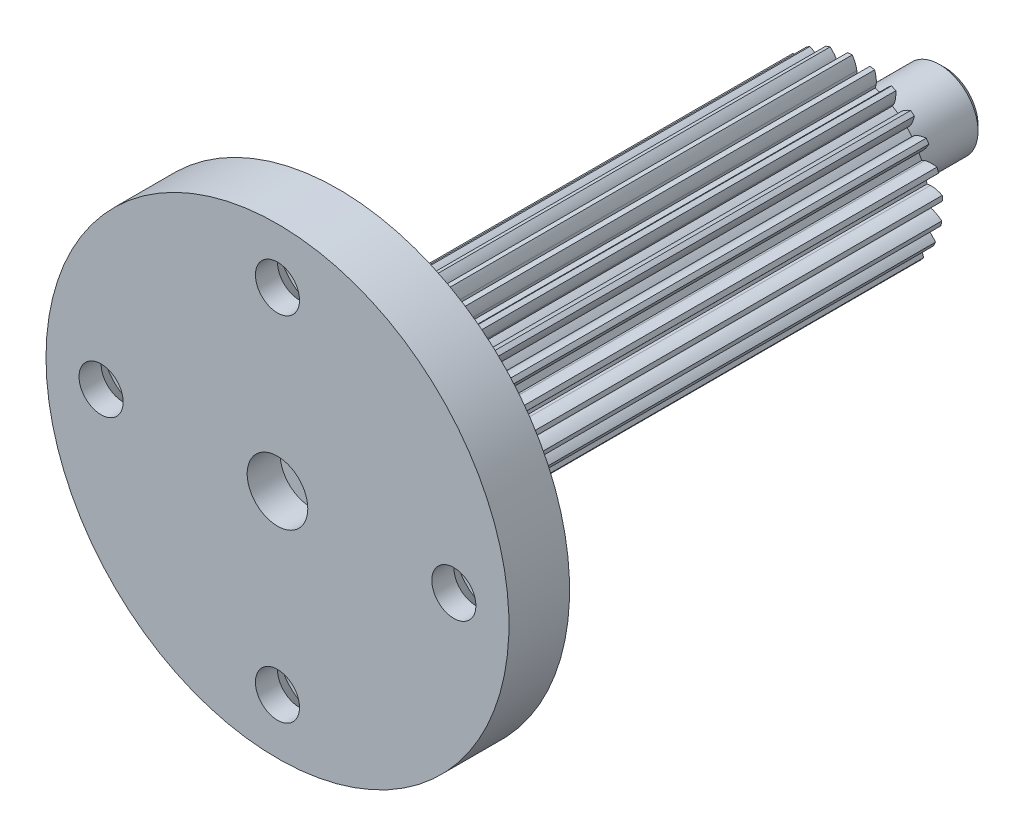
SolidWorks part; units mm, degrees
material "ABS"
ref_plane "Front Plane" through (0, 0, 0) normal (0, 0, 1) x (1, 0, 0)
ref_plane "Top Plane" through (0, 0, 0) normal (0, 1, 0) x (1, 0, 0)
ref_plane "Right Plane" through (0, 0, 0) normal (1, 0, 0) x (0, 0, -1)
sketch "Sketch1" plane through (0, 0, 0) normal (0, 0, 1) x (1, 0, 0)
  circle A0 centre (0, 0) radius 7.8
  dimension "D1" = 15.6
extrude "Boss-Extrude1" add sketch "Sketch1" along normal mid plane 48.5566
sketch "Sketch2" plane through (0, 0, 0) normal (0, 0, 1) x (1, 0, 0)
  line L0 (0, 0) -> (6.7658, 0) construction
  line L1 (0, 0) -> (7.1908, -0.3638) construction
  line L2 (0, 0) -> (6.7312, -0.6828) construction
  line L3 (6.7658, 0) -> (6.45, 0)
  line L4 (6.7312, -0.6828) -> (6.4171, -0.6509)
  circle A0 centre (0, 0) radius 7.2 construction
  circle A1 centre (0, 0) radius 6.7658 construction
  circle A2 centre (0, 0) radius 6.45
  circle A3 centre (0, 0) radius 7.8 construction
  circle A4 centre (0, 0) radius 7.8
  spline S0 degree 4 poles (6.7658, 0) (6.7681, 0) (6.7746, 0.0002) (6.7946, 0.0015) (6.834, 0.0059) (6.8824, 0.014) (6.9379, 0.0258) (6.9911, 0.0392) (7.0364, 0.052) (7.0815, 0.0658) (7.1262, 0.0806) (7.18, 0.0998) (7.2443, 0.1244) (7.3189, 0.1557) (7.4027, 0.194) (7.4874, 0.2362) (7.57, 0.2801) (7.6527, 0.3273) (7.732, 0.375) (7.8135, 0.4274) (7.8882, 0.4772) (7.9707, 0.5362) (8.037, 0.5847) (8.1231, 0.652) (8.1736, 0.6927) (8.2323, 0.7415) (8.2581, 0.7637) (8.274, 0.7774) knots 0 0 0 0 0 0.005377 0.015084 0.04661 0.092111 0.119476 0.146842 0.174209 0.201575 0.228941 0.256307 0.307035 0.361767 0.4165 0.471232 0.525964 0.580697 0.635429 0.690161 0.744894 0.799626 0.854358 0.909091 0.954545 1 1 1 1 1 construction
  spline S1 degree 4 poles (6.7658, 0) (6.7681, 0) (6.7746, 0.0002) (6.7946, 0.0015) (6.834, 0.0059) (6.8824, 0.014) (6.9379, 0.0258) (6.9911, 0.0392) (7.0364, 0.052) (7.0815, 0.0658) (7.1262, 0.0806) (7.18, 0.0998) (7.2443, 0.1244) (7.3189, 0.1557) (7.4027, 0.194) (7.4874, 0.2362) (7.57, 0.2801) (7.6527, 0.3273) (7.732, 0.375) (7.8135, 0.4274) (7.8882, 0.4772) (7.9707, 0.5362) (8.037, 0.5847) (8.1045, 0.6374) (8.1372, 0.6634) (8.1538, 0.6769) knots 0 0 0 0 0 0.005377 0.015084 0.04661 0.092111 0.119476 0.146842 0.174209 0.201575 0.228941 0.256307 0.307035 0.361767 0.4165 0.471232 0.525964 0.580697 0.635429 0.690161 0.744894 0.799626 0.854358 0.909091 0.909091 0.909091 0.909091 0.909091
  spline S2 degree 4 poles (6.7312, -0.6828) (6.7335, -0.6831) (6.74, -0.6839) (6.7598, -0.6872) (6.7985, -0.6955) (6.8459, -0.7085) (6.8999, -0.7258) (6.9515, -0.7446) (6.9953, -0.7618) (7.0387, -0.7801) (7.0816, -0.7994) (7.1333, -0.8239) (7.1948, -0.8549) (7.2658, -0.8935) (7.3454, -0.9401) (7.4254, -0.9906) (7.5031, -1.0426) (7.5806, -1.0979) (7.6547, -1.1534) (7.7304, -1.2137) (7.7997, -1.2709) (7.8759, -1.3379) (7.937, -1.3928) (8.0159, -1.4684) (8.062, -1.514) (8.1154, -1.5685) (8.1388, -1.5932) (8.1533, -1.6084) knots 0 0 0 0 0 0.005377 0.015084 0.04661 0.092111 0.119476 0.146842 0.174209 0.201575 0.228941 0.256307 0.307035 0.361767 0.4165 0.471232 0.525964 0.580697 0.635429 0.690161 0.744894 0.799626 0.854358 0.909091 0.954545 1 1 1 1 1 construction
  spline S3 degree 4 poles (6.7312, -0.6828) (6.7335, -0.6831) (6.74, -0.6839) (6.7598, -0.6872) (6.7985, -0.6955) (6.8459, -0.7085) (6.8999, -0.7258) (6.9515, -0.7446) (6.9953, -0.7618) (7.0387, -0.7801) (7.0816, -0.7994) (7.1333, -0.8239) (7.1948, -0.8549) (7.2658, -0.8935) (7.3454, -0.9401) (7.4254, -0.9906) (7.5031, -1.0426) (7.5806, -1.0979) (7.6547, -1.1534) (7.7304, -1.2137) (7.7997, -1.2709) (7.8759, -1.3379) (7.937, -1.3928) (7.9988, -1.452) (8.0287, -1.4812) (8.0439, -1.4963) knots 0 0 0 0 0 0.005377 0.015084 0.04661 0.092111 0.119476 0.146842 0.174209 0.201575 0.228941 0.256307 0.307035 0.361767 0.4165 0.471232 0.525964 0.580697 0.635429 0.690161 0.744894 0.799626 0.854358 0.909091 0.909091 0.909091 0.909091 0.909091
  dimension "D1" = 14.4
  dimension "D2" = 13.5316
  dimension "D3" = 12.9
  dimension "D4" = 2.896
  dimension "D5" = 2.896
extrude "Cut-Extrude1" cut sketch "Sketch2" against normal through all both and the other way through all contours A2 S3 A4 S1 region at (7.2227, -0.3654, 0)
pattern_circular "CirPattern2" count 24 over 360 about axis through (0, 0, -24.2783) along (0, 0, 1) of "Cut-Extrude1"
sketch "Sketch3" plane through (0, 0, 0) normal (0, 1, 0) x (1, 0, 0)
  line L0 (0, 24.2783) -> (0, 20.841) construction
  line L1 (0, 20.841) -> (0, -26.4333) construction
  line L2 (0, 32.2783) -> (-3.5, 32.2783)
  line L3 (-3.5, 32.2783) -> (-3.5, 25.7783)
  line L4 (-3.5, 25.7783) -> (-4, 25.7783)
  line L6 (-4, 25.7783) -> (-4, 24.2783)
  line L9 (0, 24.2783) -> (-4, 24.2783)
  line L10 (-4.7841, -24.2783) -> (-4.5608, -24.2783) construction
  line L11 (0, -24.2783) -> (-21, -24.2783)
  line L12 (-21, -24.2783) -> (-21, -28.2783)
  line L13 (-21, -28.2783) -> (0, -28.2783)
  line L14 (0, 32.2783) -> (0, -28.2783)
  line L15 (-4.7841, 24.2783) -> (-5.2164, 24.2783) construction
  point P7 (0, -24.2783)
  point P14 (0, 24.2783)
  dimension "D1" = 3.5
  dimension "D2" = 6.5
  dimension "D3" = 1.5
  dimension "D5" = 4
  dimension "D6" = 21
revolve "Revolve1" add sketch "Sketch3" angle 360 about L0 region at (-1.8022, 0, -28.1935) region at (-10.5, 0, 26.2783)
chamfer "Chamfer1" distance 0.5 angle 45 1 edges at (-4, 0, -24.2783)
chamfer "Chamfer2" distance 0.5 angle 45 1 edges at (-3.5, 0, -32.2783)
sketch "Sketch4" plane through (0, 0, 28.2783) normal (0, 0, 1) x (1, 0, 0)
  circle A0 centre (0, 0) radius 1.5
extrude "Cut-Extrude2" cut sketch "Sketch4" against normal through all
sketch "Sketch5" plane through (0, 0, 28.2783) normal (0, 0, 1) x (1, 0, 0)
  circle A0 centre (0, 0) radius 2.75
  dimension "D1" = 5.5
extrude "Cut-Extrude3" cut sketch "Sketch5" against normal blind 3
sketch "Sketch6" plane through (0, 0, 24.2783) normal (0, 0, -1) x (-1, 0, 0)
  circle A0 centre (0, 0) radius 16 construction
  circle A1 centre (0, 16) radius 2
  circle A2 centre (16, 0) radius 2
  circle A3 centre (0, -16) radius 2
  circle A4 centre (-16, 0) radius 2
  point P14 (0, 0)
  dimension "D1" = 32
  dimension "D2" = 4
  dimension "D3" = 4
extrude "Cut-Extrude4" cut sketch "Sketch6" against normal through all
sketch "Sketch7" plane through (0, 0, 0) normal (0, 1, 0) x (1, 0, 0)
  line L0 (14, -28.2783) -> (18, -28.2783) construction
  line L1 (18, -24.2783) -> (14, -24.2783) construction
  line L2 (14, -28.2783) -> (18, -28.2783)
  line L4 (16, -24.2783) -> (16, -28.2783) construction
  line L5 (16, -24.2783) -> (20, -24.2783)
  line L6 (20, -24.2783) -> (18, -26.2783)
  line L7 (18, -26.2783) -> (16, -26.2783)
  line L8 (16, -24.2783) -> (16, -26.2783)
  dimension "D2" = 4
revolve "Cut-Revolve1" cut sketch "Sketch7" angle 360 about L4 region at (17.5556, 0, 25.1672)
pattern_circular "CirPattern3" count 4 over 360 about axis through (0, 0, -32.2783) along (0, 0, 1) of "Cut-Revolve1"
sketch "Sketch8" plane through (0, 0, 24.2783) normal (0, 0, -1) x (-1, 0, 0)
  line L0 (0, 0) -> (0, 16) construction
  circle A0 centre (0, 16) radius 4
  circle A1 centre (16, 0) radius 4
  circle A2 centre (0, -16) radius 4
  circle A3 centre (-16, 0) radius 4
  circle A4 centre (0, 0) radius 16 construction
  point P13 (0, 0)
  dimension "D3" = 4
  dimension "D2" = 8
extrude "Cut-Extrude9" [suppressed] cut sketch "Sketch8" along normal blind 6.5
sketch "Sketch9" plane through (0, 0, 24.2783) normal (0, 0, -1) x (-1, 0, 0)
  circle A0 centre (0, 0) radius 21
  circle A2 centre (0, 0) radius 21 construction
  circle A3 centre (16, 0) radius 4 construction
  circle A4 centre (0, -16) radius 4 construction
  circle A5 centre (-16, 0) radius 4 construction
  circle A6 centre (0, 16) radius 4 construction
  circle A7 centre (16, 0) radius 4
  circle A8 centre (0, -16) radius 4
  circle A9 centre (-16, 0) radius 4
  circle A10 centre (0, 16) radius 4
  circle A11 centre (0, 0) radius 1.5 construction
  circle A12 centre (0, 0) radius 1.5
extrude "Boss-Extrude2" add sketch "Sketch9" along normal blind 1.5
sketch "Sketch10" plane through (0, 0, 0) normal (0, 1, 0) x (1, 0, 0)
  line L0 (-4.7841, -22.7783) -> (12, -22.7783)
  line L1 (20, -22.7783) -> (12, -22.7783) construction
  line L2 (21, -22.7783) -> (-21, -22.7783) construction
  line L3 (12, -22.7783) -> (7.8, -17.7783)
  line L4 (7.8, -17.7783) -> (-4.7841, -17.7783)
  line L5 (-4.7841, 24.2783) -> (-4.7841, -22.7783) construction
  line L6 (-4.7841, -17.7783) -> (-4.7841, -22.7783)
  line L7 (0, 0) -> (0, -28.6082) construction
  line L8 (0, -17.7783) -> (0, -22.7783)
  dimension "D1" = 7.8
  dimension "D2" = 5
  dimension "D3" = 12
  dimension "D4" = 12
revolve "Revolve2" add sketch "Sketch10" angle 360 about L7 region at (5.0242, 0, 20.4551)
equation "\"Ns\"= 24"
equation "\"module\"= 0.6"
equation "\"pressure angle\"= 20.0"
equation "\"h_a\"= 0.6"
equation "\"h_b\"= 0.75"
equation "\"clr_tip_root\"= 0.15000000000000002"
equation "\"dp_s\"= 14.399999999999999"
equation "\"db_s\"= 13.53157373931708"
equation "\"D1@Sketch1\"=\"dp_s\" + 2*\"h_a\""
equation "\"fw_s_calc\"= 16.210783717444997"
equation "\"D1@Boss-Extrude1\"=\"fw_s_used\""
equation "\"D1@Sketch2\"=\"dp_s\""
equation "\"D2@Sketch2\"= \"db_s\""
equation "\"D3@Sketch2\"=\"dp_s\"- 2*\"h_b\""
equation "\"alpha_s\"= 0.8539582918412343"
equation "\"D4@Sketch2\"= 360 / ( 4 * \"Ns\" ) - \"alpha_s\""
equation "\"beta_s\"= 5.792083416317531"
equation "\"D5@Sketch2\"= 360 / ( 4 * \"Ns\" ) - \"alpha_s\""
equation "\"D1@CirPattern2\"=\"Ns\""
equation "\"Nr\"= 78"
equation "\"pressure_angle\"= 20.0"
equation "\"h_f\"= 0.75"
equation "\"dp_r\"= 46.8"
equation "\"db_r\"= 43.97761465278051"
equation "\"fw_r\"= 22.845791438896047"
equation "\"alpha_r\"= 0.8539582918412556"
equation "\"beta_r\"= 4.015608891374819"
equation "\"bearing_ID\"= 45"
equation "\"bearing_OD\"= 58"
equation "\"bearing_height\"= 7"
equation "\"clearance_planet\"= 1.5"
equation "\"case_dist\"= 24.210783717444997"
equation "\"Motor_case_OD_max\"= 88.5"
equation "\"case_mounting_PCD\"= 81.0"
equation "\"bearing mount thickness\"= IIF((\"bearing_OD\" + \"output_mounting_hole_dia\" * 4) > (\"Nr\" * \"module\" + 2 * \"h_b\"), \"output_mounting_hole_dia\" * 2, ((\"Nr\" * \"module\" + 2 * \"h_b\" - (\"bearing_OD\" + \"output_mounting_hole_dia\" * 4)) / 2) + \"output_mounting_hole_dia\" * 2 + \"standard_clearance_1_5mm\")"
equation "\"case_mounting_hole_dia\"= 3"
equation "\"output_mounting_PCD\"= 66"
equation "\"output_mounting_hole_dia\"= 4"
equation "\"clearance_case_mount_holes_shell_thickness\"= 1"
equation "\"motor_case_OD_base\"= 79.0"
equation "\"sec_carrier_thickness\"= 5"
equation "\"sun_coupler_hub_thickness\"= 4"
equation "\"clearance_sun_coupler_sec_carrier\"= 1.5"
equation "\"clearance_motor_and_case\"= 5"
equation "\"motor_OD\"= 64"
equation "\"Motor_case_thickness\"= 2.5"
equation "\"Motor_case_ID\"= 74"
equation "\"case_mounting_hole_shift\"= 1.0"
equation "\"output_mounting_nut_wrench_size\"= 7"
equation "\"output_mounting_nut_thickness\"= 3.2"
equation "\"case_mounting_hole_allen_socket_dia\"= 5.5"
equation "\"output_mounting_nut_depth\"= 3"
equation "\"case_mounting_bolt_depth\"= 4.5"
equation "\"ring_radial_thickness\"= 7.100000000000001"
equation "\"ring_OD\"= 61.0"
equation "\"ring_to_chamfer_clearance\"= 0.5"
equation "\"Motor_case_OD_base_to_chamfer\"= 5"
equation "\"pattern_offset_from_motor_case_OD_base\"= 3"
equation "\"pattern_bulge_dia\"= 3"
equation "\"pattern_num_bulge\"= 18"
equation "\"pattern_depth\"= 2"
equation "\"motor_height\"= 75"
equation "\"case_mounting_wrench_size\"= 5.5"
equation "\"case_mounting_nut_clearance\"= 2"
equation "\"base_plate_thickness\"= 4"
equation "\"case_mounting_nut_thickness\"= 2.4"
equation "\"case_mounting_surface_height\"= 4"
equation "\"motor_mount_hole_PCD\"= 44"
equation "\"motor_mount_hole_dia\"= 4"
equation "\"motor_mount_hole_num\"= 4"
equation "\"central_hole_offset_from_motor_mount_PCD\"= 5"
equation "\"wire_slot_dist_from_center\"= 22"
equation "\"wire_slot_length\"= 8"
equation "\"wire_slot_radius\"= 2"
equation "\"driver_upper_holes_dist_from_center\"= 29"
equation "\"driver_lower_holes_dist_from_center\"= 13"
equation "\"driver_side_holes_dist_from_center\"= 22.5"
equation "\"driver_mount_holes_dia\"= 3"
equation "\"driver_mount_inserts_OD\"= 4.8"
equation "\"driver_mount_thickness\"= 1.5"
equation "\"driver_mount_height\"= 6"
equation "\"air_flow_hole_offset\"= 3"
equation "\"num_planet\"= 3"
equation "\"planet_pin_bolt_dia\"= 2.5"
equation "\"planet_pin_socket_head_dia\"= 4.5"
equation "\"carrier_PCD\"= 34.199999999999996"
equation "\"planet_shaft_dia\"= 5"
equation "\"planet_shaft_step_offset\"= 0.8"
equation "\"carrier_trapezoidal_support_sun_offset\"= 5"
equation "\"carrier_trapezoidal_support_hole_PCD_offset_bearing_ID\"= 4"
equation "\"carrier_trapezoidal_support_hole_dia\"= 3"
equation "\"carrier_trapezoidal_support_hole_socket_head_dia\"= 5.5"
equation "\"carrier_bearing_step_width\"= 1.5"
equation "\"standard_clearance_1_5mm\"= 1.5"
equation "\"standard_fillet_1_5mm\"= 1.5"
equation "\"sun_shaft_bearing_OD\"= 14"
equation "\"sun_shaft_bearing_width\"= 5"
equation "\"standard_bearing_insertion_chamfer\"= 0.5"
equation "\"carrier_trapezoidal_support_hole_wrench_size\"= 5.5"
equation "\"planet_pin_bolt_wrench_size\"= 5"
equation "\"planet_bearing_OD\"= 8"
equation "\"planet_bearing_width\"= 2.5"
equation "\"planet_bore\"= 6"
equation "\"motor_output_hole_PCD\"= 32"
equation "\"motor_output_hole_dia\"= 4"
equation "\"motor_output_hole_num\"= 4"
equation "\"sun_shaft_bearing_ID\"= 7"
equation "\"D1@Sketch3\"=\"sun_shaft_bearing_ID\"/2"
equation "\"D2@Sketch3\"=\"sun_shaft_bearing_width\" + \"standard_clearance_1_5mm\""
equation "\"D3@Sketch3\"=\"standard_clearance_1_5mm\""
equation "\"D4@Sketch3\"=\"standard_clearance_1_5mm\"/3"
equation "\"D5@Sketch3\"=\"sun_coupler_hub_thickness\""
equation "\"sun_hub_dia\"= 42.0"
equation "\"D6@Sketch3\"=\"sun_hub_dia\"/2"
equation "\"D1@Chamfer2\"=\"standard_bearing_insertion_chamfer\""
equation "\"D1@Chamfer1\"=\"standard_bearing_insertion_chamfer\""
equation "\"sun_central_bolt_dia\"= 3"
equation "\"sun_central_bolt_socket_head_dia\"= 5.5"
equation "\"D1@Sketch4\"=\"sun_central_bolt_dia\""
equation "\"D1@Cut-Extrude3\"=\"sun_central_bolt_dia\""
equation "\"D1@Sketch5\"=\"sun_central_bolt_socket_head_dia\" "
equation "\"fw_s_used\"= 48.55657515634104"
equation "\"D1@Sketch6\"=\"motor_output_hole_PCD\""
equation "\"D2@Sketch6\"=\"motor_output_hole_dia\""
equation "\"D3@Sketch6\"=\"motor_output_hole_num\""
equation "\"motor_output_hole_CSK_OD\"= 8"
equation "\"motor_output_hole_CSK_head_height\"= 2.0"
equation "\"D2@Sketch7\"=\"motor_output_hole_CSK_OD\"/2"
equation "\"D3@Sketch7\"=\"motor_output_hole_dia\"/2"
equation "\"D1@CirPattern3\"=\"motor_output_hole_num\""
equation "\"Np_b\"= 33"
equation "\"dp_p_b\"= 19.8"
equation "\"db_p_b\"= 18.605913891560988"
equation "\"fw_p_s\"= 24.345791438896047"
equation "\"alpha_p_b\"= 0.8539582918412414"
equation "\"beta_p_b\"= 3.7466288708629714"
equation "\"bearing_retainer_thickness\"= 2"
equation "\"Np_s\"= 21"
equation "\"fw_p_b\"= 16.210783717444997"
equation "\"dp_p_s\"= 12.6"
equation "\"db_p_s\"= 11.840127021902445"
equation "\"alpha_p_s\"= 0.8539582918412556"
equation "\"beta_p_s\"= 6.86351198774606"
equation "\"D1@Sketch8\"=\"motor_output_hole_PCD\"/2"
equation "\"D2@Sketch8\"=\"motor_output_hole_CSK_OD\""
equation "\"D1@Sketch7\"=\"motor_output_hole_CSK_head_height\""
equation "\"D1@Cut-Extrude9\"=\"sec_carrier_thickness\"+\"standard_clearance_1_5mm\""
equation "\"Cut-Extrude9\"= IIF ( ( \"Ns\" * \"module\" + 2 * \"h_a\" ) < ( \"motor_output_hole_PCD\" - \"motor_output_hole_CSK_OD\" ) , \"suppressed\" , \"unsuppressed\" )"
equation "\"D3@Sketch8\"=\"motor_output_hole_num\""
equation "\"bearing_mount_thickness\"= 8"
equation "\"tight_clearance_3DP\" = 0.4"
equation "\"loose_clearance_3DP\" = 0.8"
equation "\"D1@Boss-Extrude2\"=\"clearance_sun_coupler_sec_carrier\""
equation "\"D1@Sketch10\"=(\"Ns\" * \"module\" + \"h_a\"*2)/2"
equation "\"D2@Sketch10\"=\"sec_carrier_thickness\""
equation "\"D3@Sketch10\"=(\"motor_output_hole_PCD\" - \"motor_output_hole_CSK_OD\")/2"
equation "\"D1@Fillet1\"=\"standard_fillet_1_5mm\"/3"
equation "\"Boss-Extrude2\"= IIF ( ( \"Ns\" * \"module\" + 2 * \"h_a\" ) < ( \"motor_output_hole_PCD\" - \"motor_output_hole_CSK_OD\" ) , \"unsuppressed\" , \"suppressed\" )"
equation "\"Revolve2\"= IIF ( ( \"Ns\" * \"module\" + 2 * \"h_a\" ) < ( \"motor_output_hole_PCD\" - \"motor_output_hole_CSK_OD\" ) , \"unsuppressed\" , \"suppressed\" )"
equation "\"Fillet1\"= IIF ( ( \"Ns\" * \"module\" + 2 * \"h_a\" ) < ( \"motor_output_hole_PCD\" - \"motor_output_hole_CSK_OD\" ) , \"unsuppressed\" , \"suppressed\" )"
equation "\"D4@Sketch10\"=\"D3@Sketch10\""
